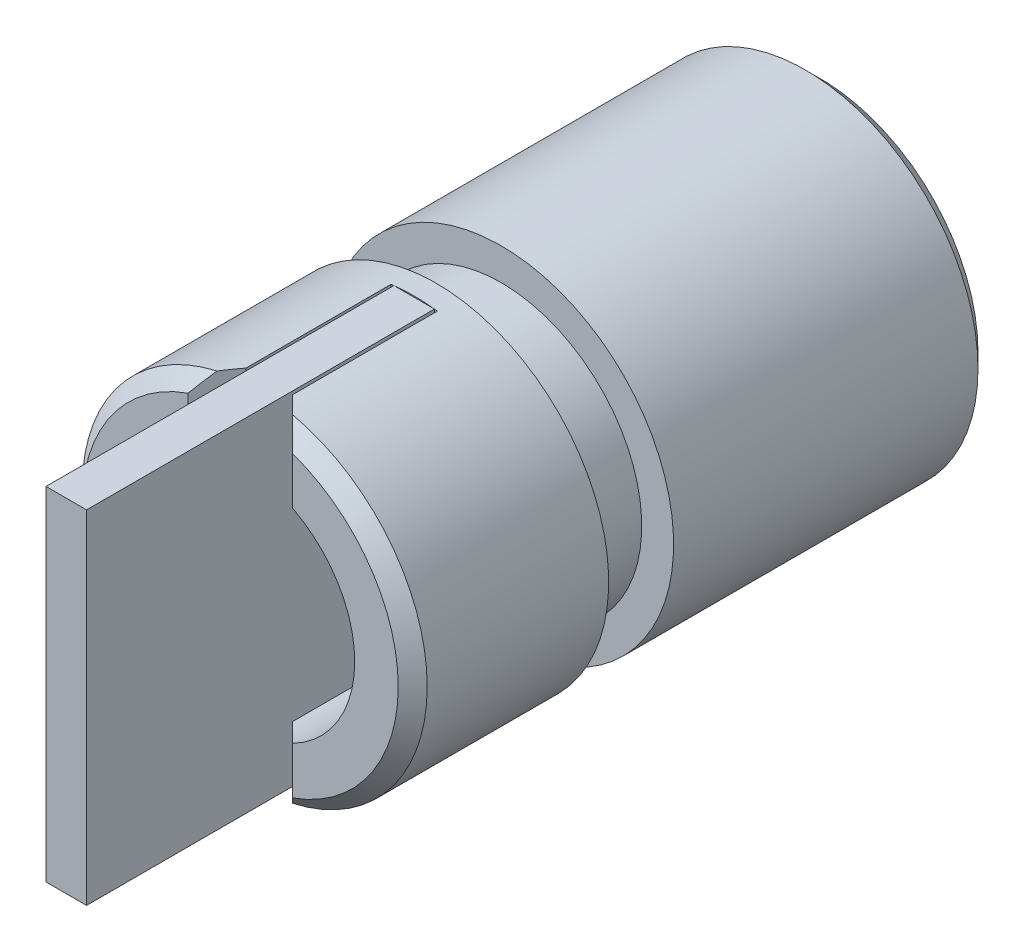
SolidWorks part; units mm, degrees
ref_plane "Plano frontal" through (0, 0, 0) normal (0, 0, 1) x (1, 0, 0)
ref_plane "Plano superior" through (0, 0, 0) normal (0, 1, 0) x (1, 0, 0)
ref_plane "Plano direito" through (0, 0, 0) normal (1, 0, 0) x (0, 0, -1)
sketch "Esboço1" plane through (0, 0, 0) normal (0, 0, 1) x (1, 0, 0)
  circle A0 centre (0, 0) radius 2.975
  dimension "D1" = 5.95
extrude "Ressalto-extrusão1" add sketch "Esboço1" along normal blind 10
ref_plane "Plano1" through (0, 0, 5.5) normal (0, 0, -1) x (-1, 0, 0)
sketch "Esboço2" plane through (0, 0, 5.5) normal (0, 0, -1) x (-1, 0, 0)
  circle A0 centre (0, 0) radius 4.0731
  circle A1 centre (0, 0) radius 2.425
  dimension "D1" = 4.85
extrude "Corte-extrusão1" cut sketch "Esboço2" against normal blind 1.12
sketch "Esboço3" plane through (0, 0, 0) normal (0, 0, -1) x (-1, 0, 0)
  circle A0 centre (0, 0) radius 1.455
  circle A1 centre (0, 0) radius 2.975 construction
  dimension "D1" = 1.52
extrude "Corte-extrusão2" cut sketch "Esboço3" against normal blind 1
sketch "Esboço4" plane through (0, 0, 10) normal (0, 0, 1) x (1, 0, 0)
  circle A0 centre (0, 0) radius 1.975
  circle A1 centre (0, 0) radius 2.975 construction
  dimension "D1" = 1
extrude "Corte-extrusão3" cut sketch "Esboço4" against normal up to surface (9 mm away) up to face at (-1.455, 0, 1)
sketch "Esboço5" plane through (0, 0, 1) normal (0, 0, 1) x (1, 0, 0)
  circle A0 centre (0, 0) radius 1.975
extrude "Ressalto-extrusão2" add sketch "Esboço5" along normal blind 0.5
chamfer "Chanfro1" distance 0.25 angle 45 2 edges at (2.975, 0, 10) (2.975, 0, 0)
sketch "Esboço6" plane through (0, 0, 10) normal (0, 0, 1) x (1, 0, 0)
  line L1 (0.4, 3.3418) -> (-0.4, 3.3418)
  line L2 (0.4, 3.3418) -> (0.4, -3.3418)
  line L3 (0.4, -3.3418) -> (-0.4, -3.3418)
  line L4 (-0.4, 3.3418) -> (-0.4, -3.3418)
  line L5 (0.4, 3.3418) -> (-0.4, -3.3418) construction
  line L6 (0.4, -3.3418) -> (-0.4, 3.3418) construction
  point P0 (0, 0)
  dimension "D1" = 0.8
extrude "Corte-extrusão4" cut sketch "Esboço6" against normal blind 3
chamfer "Chanfro2" distance 0.5 angle 45 4 edges at (0.4, -2.3148, 10) (-0.4, -2.3148, 10) (0.4, 2.3148, 10) (-0.4, 2.3148, 10)
sketch "Esboço7" plane through (0, 0, 7) normal (0, 0, 1) x (1, 0, 0)
  line L0 (-0.4, 2.948) -> (-0.4, 1.9341) construction
  line L1 (0.35, 2.9543) -> (-0.35, 2.9543)
  line L2 (0.35, 2.9543) -> (0.35, -2.9543)
  line L3 (0.35, -2.9543) -> (-0.35, -2.9543)
  line L4 (-0.35, 2.9543) -> (-0.35, -2.9543)
  line L5 (0.35, 2.9543) -> (-0.35, -2.9543) construction
  line L6 (0.35, -2.9543) -> (-0.35, 2.9543) construction
  arc A0 (-0.4, -2.948) -> (0.4, -2.948) centre (0, 0) ccw construction
  point P0 (0, 0)
  dimension "D1" = 0.05
extrude "Ressalto-extrusão3" add sketch "Esboço7" along normal blind 6
